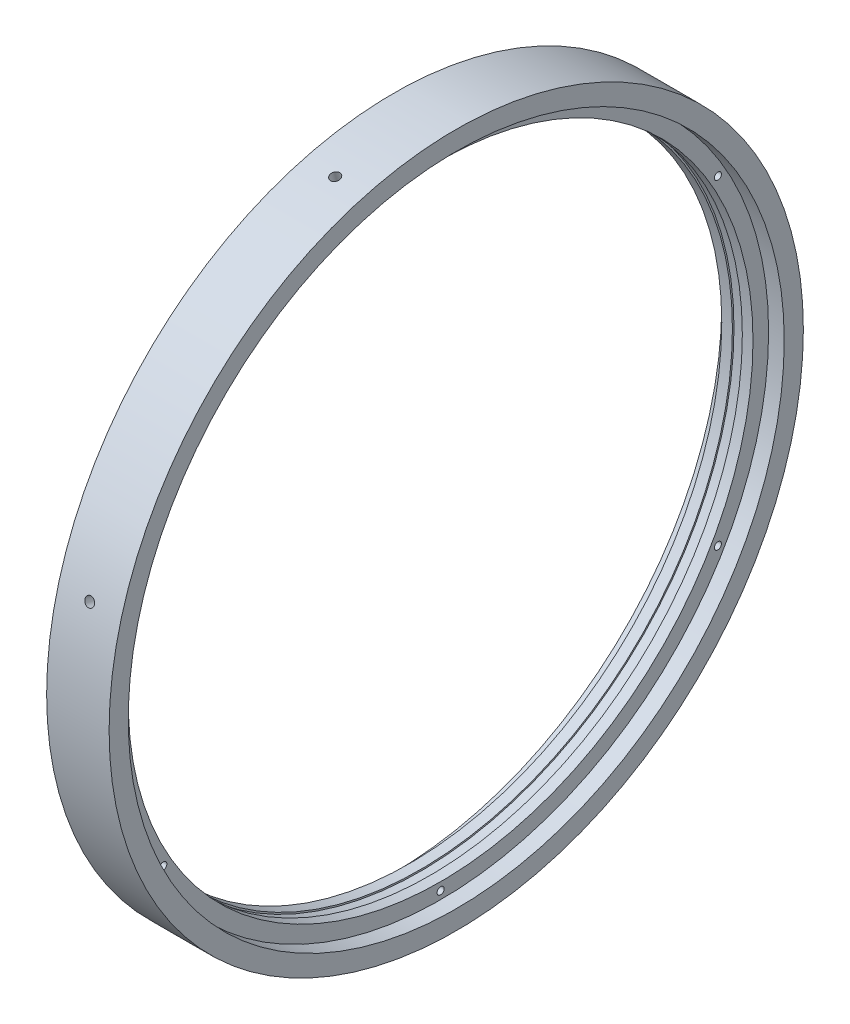
SolidWorks part; units mm, degrees
material "Delrin 2700 NC010, Low Viscosity Acetal Copolymer (SS)"
ref_plane "Front Plane" through (0, 0, 0) normal (0, 0, 1) x (1, 0, 0)
ref_plane "Top Plane" through (0, 0, 0) normal (0, 1, 0) x (1, 0, 0)
ref_plane "Right Plane" through (0, 0, 0) normal (1, 0, 0) x (0, 0, -1)
sketch "Sketch3" plane through (0, 0, 0) normal (0, 1, 0) x (1, 0, 0)
  line L0 (0, 0) -> (0, -111.125) construction
  line L1 (-10, -111.125) -> (10, -111.125)
  line L2 (10, -111.125) -> (10, -105)
  line L3 (10, -105) -> (5, -105)
  line L4 (5, -105) -> (5, -100)
  line L5 (5, -100) -> (1.5875, -100)
  line L6 (1.5875, -100) -> (1.5875, -100.5)
  line L7 (1.5875, -100.5) -> (-1.5875, -100.5)
  line L8 (-10, -111.125) -> (-10, -105)
  line L9 (-10, -105) -> (-5, -105)
  line L10 (-5, -105) -> (-5, -100)
  line L11 (-5, -100) -> (-1.5875, -100)
  line L12 (-1.5875, -100) -> (-1.5875, -100.5)
  line L13 (0, 0) -> (-91.3824, 0) construction
  point P16 (0, -100.5)
  dimension "D1" = 111.125
  dimension "D2" = 10
  dimension "D3" = 100
  dimension "D4" = 5
  dimension "D5" = 5
  dimension "D6" = 1.5875
  dimension "D7" = 0.5
revolve "Revolve1" add sketch "Sketch3" angle 360 about L13
sketch "Sketch4" plane through (5, 0, 0) normal (1, 0, 0) x (0, 0, -1)
  line L0 (0, 0) -> (0, -102.5) construction
  line L1 (0, 0) -> (-88.7676, -51.25) construction
  line L2 (0, 0) -> (-88.7676, 51.25) construction
  line L3 (0, 0) -> (0, 102.5) construction
  line L4 (0, 0) -> (88.7676, 51.25) construction
  line L5 (0, 0) -> (88.7676, -51.25) construction
  circle A0 centre (0, 0) radius 102.5 construction
  circle A1 centre (0, 0) radius 105
  circle A2 centre (0, 0) radius 105
  dimension "D2" = 205
  dimension "D1" = 0
  dimension "D3" = 6
hole_wizard "Tap Drill for #4-40 Tap2" positions "3DSketch1" profile "Sketch5" hole size "#4-40" standard "Ansi Inch"
sketch3d "3DSketch1"
  point P0 (5, -102.5, 0)
  point P3 (5, -51.25, -88.7676)
  point P6 (5, -51.25, 88.7676)
  point P9 (5, 51.25, 88.7676)
  point P12 (5, 102.5, 0)
  point P15 (5, 51.25, -88.7676)
sketch "Sketch5" plane through (5, -102.5, 0) normal (0, 1, 0) x (0, 0, -1)
  line L0 (0, 0) -> (0, 9.5692)
  line L1 (0, 9.5692) -> (1.1303, 8.89)
  line L2 (1.1303, 8.89) -> (1.1303, 0)
  line L5 (1.1303, 0) -> (0, 0)
  line L10 (0, 9.5692) -> (-1.1303, 8.89) construction
  line L11 (0, -6.35) -> (0, 107.95) construction
  dimension "Hole Dia." = 2.2606
  dimension "Hole Depth" = 8.89
  dimension "Drill Angle" = 118
sketch "Sketch6" plane through (-5, 0, 0) normal (-1, 0, 0) x (0, 0, 1)
  line L0 (0, 0) -> (0, -102.5) construction
  line L1 (0, 0) -> (51.25, -88.7676) construction
  line L2 (0, 0) -> (-51.25, -88.7676) construction
  line L3 (0, 0) -> (-102.5, 0) construction
  line L4 (0, 0) -> (-51.25, 88.7676) construction
  line L5 (0, 0) -> (51.25, 88.7676) construction
  line L6 (0, 0) -> (102.5, 0) construction
  circle A0 centre (0, 0) radius 102.5
  circle A1 centre (0, 0) radius 105
  circle A2 centre (0, 0) radius 105
  dimension "D2" = 205
  dimension "D3" = 30
  dimension "D1" = 0
  dimension "D4" = 6
hole_wizard "Tap Drill for #4-40 Tap3" positions "3DSketch2" profile "Sketch7" hole size "#4-40" standard "Ansi Inch"
sketch3d "3DSketch2"
  point P0 (-5, -88.7676, 51.25)
  point P3 (-5, 0, 102.5)
  point P6 (-5, 88.7676, -51.25)
  point P9 (-5, 88.7676, 51.25)
  point P12 (-5, 0, -102.5)
  point P15 (-5, -88.7676, -51.25)
sketch "Sketch7" plane through (-5, -88.7676, 51.25) normal (0, 1, 0) x (0, 0, 1)
  line L0 (0, 0) -> (0, 9.5692)
  line L1 (0, 9.5692) -> (1.1303, 8.89)
  line L2 (1.1303, 8.89) -> (1.1303, 0)
  line L5 (1.1303, 0) -> (0, 0)
  line L10 (0, 9.5692) -> (-1.1303, 8.89) construction
  line L11 (0, -6.35) -> (0, 107.95) construction
  dimension "Hole Dia." = 2.2606
  dimension "Hole Depth" = 8.89
  dimension "Drill Angle" = 118
ref_plane "Plane1" through (0, 107.3385, 28.7613) normal (0, 0.9659, 0.2588) x (-1, 0, 0)
sketch "Sketch9" plane through (0, 107.3385, 28.7613) normal (0, 0.9659, 0.2588) x (-1, 0, 0)
  line L0 (0, 0) -> (-10, 0) construction
  line L1 (-10, 111.125) -> (-10, -111.125) construction
  circle A0 centre (0, 0) radius 1.524
  dimension "D1" = 3.048
extrude "Cut-Extrude1" cut sketch "Sketch9" against normal blind 8.89
ref_axis "Axis1" through (-10, 0, 0) along (1, 0, 0)
pattern_circular "CirPattern1" count 6 over 360 about axis through (-10, 0, 0) along (1, 0, 0) of "Cut-Extrude1"
sketch "Sketch10" plane through (-10, 0, 0) normal (-1, 0, 0) x (0, 0, 1)
  circle A0 centre (0, 0) radius 105 construction
  circle A1 centre (0, 0) radius 111.125
  circle A2 centre (0, 0) radius 111.125
  circle A3 centre (0, 0) radius 105
  circle A4 centre (0, 0) radius 108.0625 construction
  point P6 (0, 108.0625)
  point P7 (93.5849, 54.0312)
  point P10 (93.5849, -54.0313)
  point P11 (0, -108.0625)
  point P12 (-93.5849, -54.0312)
  point P13 (-93.5849, 54.0313)
  dimension "D2" = 216.125
  dimension "D1" = 0
  dimension "D3" = 6
hole_wizard "Tap Drill for #4-40 Tap1" positions "3DSketch3" profile "Sketch11" hole size "#4-40" standard "Ansi Inch"
sketch3d "3DSketch3"
  point P0 (-10, 108.0625, 0)
  point P3 (-10, 54.0312, 93.5849)
  point P6 (-10, -54.0313, 93.5849)
  point P9 (-10, -108.0625, 0)
  point P12 (-10, -54.0312, -93.5849)
  point P15 (-10, 54.0313, -93.5849)
sketch "Sketch11" plane through (-10, 108.0625, 0) normal (0, 1, 0) x (0, 0, 1)
  line L0 (0, 0) -> (0, 7.0292)
  line L1 (0, 7.0292) -> (1.1303, 6.35)
  line L2 (1.1303, 6.35) -> (1.1303, 0)
  line L5 (1.1303, 0) -> (0, 0)
  line L10 (0, 7.0292) -> (-1.1303, 6.35) construction
  line L11 (0, -6.35) -> (0, 107.95) construction
  dimension "Hole Dia." = 2.2606
  dimension "Hole Depth" = 6.35
  dimension "Drill Angle" = 118
